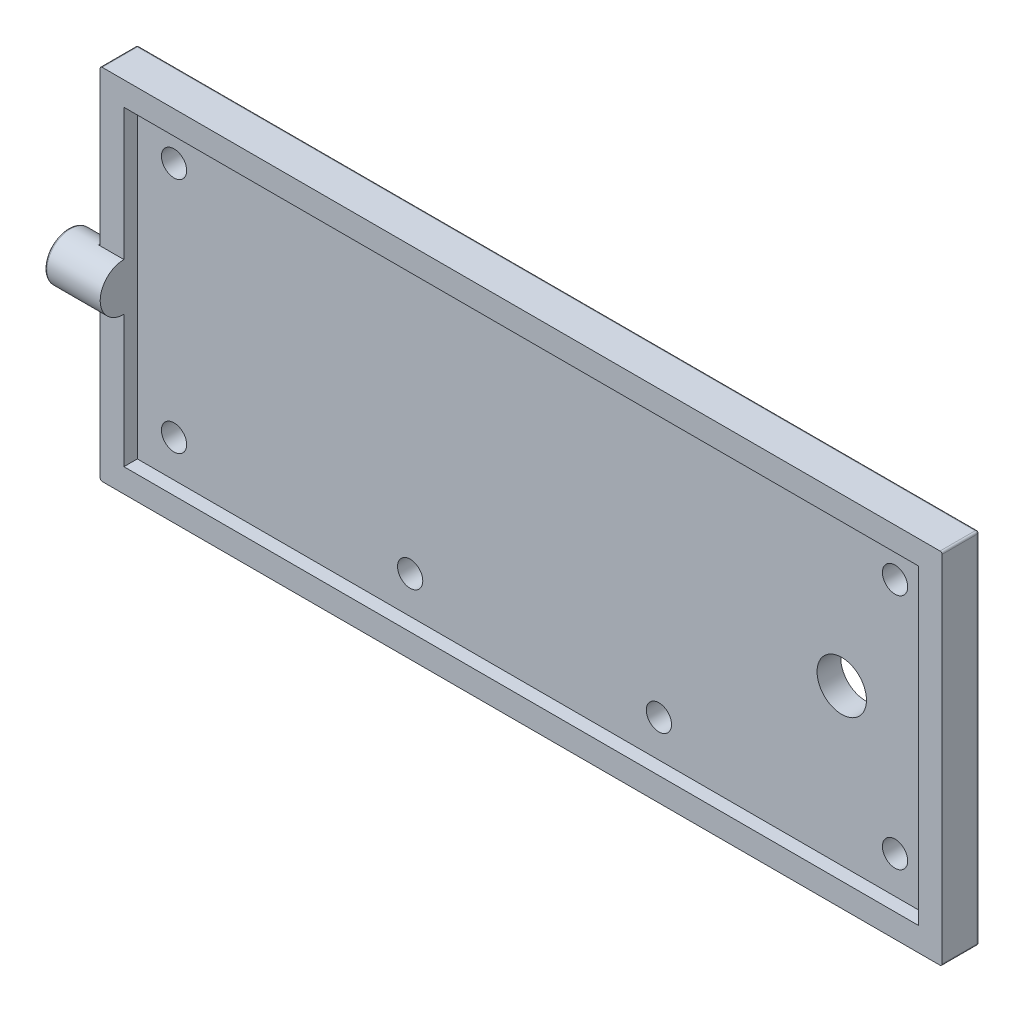
SolidWorks part; units mm, degrees
ref_plane "Front Plane" through (0, 0, 0) normal (0, 0, 1) x (1, 0, 0)
ref_plane "Top Plane" through (0, 0, 0) normal (0, 1, 0) x (1, 0, 0)
ref_plane "Right Plane" through (0, 0, 0) normal (1, 0, 0) x (0, 0, -1)
sketch "Sketch1" plane through (0, 0, 0) normal (0, 0, 1) x (1, 0, 0)
  line L0 (92.08, 42.37) -> (92.08, 3) construction
  line L1 (0, 0) -> (106.46, 0)
  line L2 (0, 0) -> (0, 45.37)
  line L3 (0, 45.37) -> (106.46, 45.37)
  line L4 (106.46, 0) -> (106.46, 45.37)
  line L5 (3, 3) -> (103.46, 3)
  line L6 (3, 3) -> (3, 42.37)
  line L7 (3, 42.37) -> (103.46, 42.37)
  line L8 (103.46, 3) -> (103.46, 42.37)
  circle A0 centre (7.64, 7.68) radius 1.595
  circle A1 centre (37.5, 7.68) radius 1.595
  circle A2 centre (68.96, 7.68) radius 1.595
  circle A3 centre (98.82, 7.68) radius 1.595
  circle A4 centre (7.64, 37.69) radius 1.595
  circle A5 centre (98.82, 37.69) radius 1.595
  circle A6 centre (92.08, 22.685) radius 3.125
  point P25 (0, 0)
  point P26 (0, 0)
  dimension "D7" = 3.19
  dimension "D8" = 3.19
  dimension "D9" = 3.19
  dimension "D10" = 3.19
  dimension "D11" = 3.19
  dimension "D14" = 3.19
  dimension "D19" = 6.25
  dimension "D1" = 45.37
  dimension "D2" = 106.46
  dimension "D3" = 3
  dimension "D4" = 3
  dimension "D5" = 3
  dimension "D6" = 3
  dimension "D12" = 4.68
  dimension "D13" = 4.64
  dimension "D15" = 4.68
  dimension "D16" = 29.86
  dimension "D17" = 31.46
  dimension "D18" = 29.86
  dimension "D20" = 11.38
extrude "Boss-Extrude1" add sketch "Sketch1" along normal blind 3 contours L0 L7 L6 L5 A6 A4 A2 A1 A0 | L7 L0 A6 L5 L8 A3 A5 region at (97.8904, 22.685, 0) region at (47.5065, 22.7543, 0)
extrude "Boss-Extrude2" add sketch "Sketch1<5>" along normal blind 4.7 contours L1 L4 L3 L2 L8 L5 L6 L7 region at (1.1572, 22.685, 0)
sketch "Sketch1<5>" plane through (0, 0, 0) normal (0, 0, 1) x (1, 0, 0) same geometry as "Sketch1"
sketch "Sketch2" plane through (0, 0, 0) normal (-1, 0, 0) x (0, 0, 1)
  line L0 (4.7, 0) -> (4.7, 45.37) construction
  circle A0 centre (4.7, 22.685) radius 3
extrude "Boss-Extrude3" add sketch "Sketch2" along normal blind 4 and the other way blind 3
fillet "Fillet1" radius 0.25 10 edges at (-4, 22.685, 7.7) (0, 45.37, 2.35) (53.23, 45.37, 0) (106.46, 45.37, 2.35) (106.46, 0, 2.35) (106.46, 22.685, 0) (0, 0, 2.35) (53.23, 0, 0) (0, 22.685, 0) (0, 22.685, 1.7)
